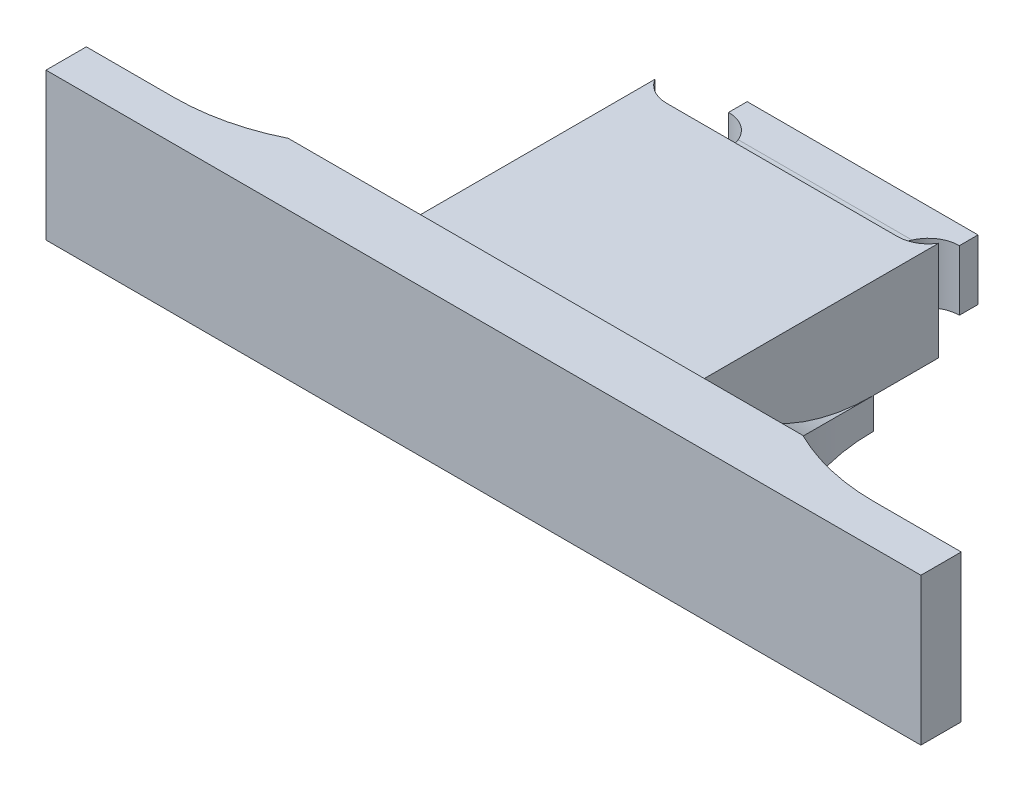
SolidWorks part; units mm, degrees
ref_plane "Front Plane" through (0, 0, 0) normal (0, 0, 1) x (1, 0, 0)
ref_plane "Top Plane" through (0, 0, 0) normal (0, 1, 0) x (1, 0, 0)
ref_plane "Right Plane" through (0, 0, 0) normal (1, 0, 0) x (0, 0, -1)
sketch "Sketch2" plane through (0, 0, 138.6086) normal (0, 0, 1) x (1, 0, 0)
  line L0 (70.4445, 0) -> (70.4445, 5) construction
  line L1 (-70.5526, 0) -> (70.4445, 0)
  line L2 (-70.5526, 0) -> (-70.5526, 23.7194)
  line L3 (-70.5526, 23.7194) -> (70.4445, 23.7194)
  line L4 (70.4445, 0) -> (70.4445, 23.7194)
extrude "Boss-Extrude1" add sketch "Sketch2" along normal blind 40
sketch "Sketch3" plane through (-70.5526, 0, 0) normal (-1, 0, 0) x (0, 0, 1)
  line L0 (138.6086, 23.7194) -> (138.6086, 0) construction
  line L3 (138.6086, 5) -> (152.3731, 5)
  line L4 (178.6086, 23.7194) -> (138.6086, 23.7194) construction
  line L5 (158.6086, 23.7194) -> (178.6086, 23.7194)
  line L8 (138.6086, 23.7194) -> (138.6086, 0)
  line L9 (138.6086, 0) -> (178.6086, 0)
  line L10 (178.6086, 0) -> (178.6086, 23.7194)
  line L11 (178.6086, 23.7194) -> (138.6086, 23.7194)
  line L12 (138.6086, 23.7194) -> (138.6086, 0)
  line L13 (138.6086, 0) -> (178.6086, 0)
  line L14 (178.6086, 0) -> (178.6086, 23.7194)
  line L15 (178.6086, 23.7194) -> (138.6086, 23.7194)
  arc A0 (138.6086, 5) -> (168.6086, 23.7194) centre (138.6086, 38.399) ccw
  point P2 (158.6086, 23.7194)
  point P21 (168.6086, 23.7194)
  line M6 (138.6086, 23.7194) -> (138.6086, 0)
  line M9 (178.6086, 23.7194) -> (138.6086, 23.7194)
  dimension "D2" = 5
  dimension "D3" = 23.7194
  dimension "D1" = 0
extrude "Cut-Extrude1" cut sketch "Sketch3" against normal through all contours M6 M9 region at (-70.5526, 16.0164, 150.4428)
sketch "Sketch4" plane through (0, 5, 0) normal (0, 1, 0) x (1, 0, 0)
  line L0 (-0.0541, -138.6086) -> (-0.0541, -183.6086)
  line L1 (70.4445, -138.6086) -> (-70.5526, -138.6086) construction
  line L2 (70.4445, -168.6086) -> (-70.5526, -168.6086) construction
  line L4 (-22.9249, -168.6086) -> (-22.9249, -128.1086)
  line L9 (-0.6345, -168.6086) -> (0.8576, -168.6086) construction
  line L10 (22.8168, -168.6086) -> (-22.9249, -168.6086)
  line L11 (22.8168, -168.6086) -> (22.8168, -128.1086)
  line L15 (-18.6541, -120.5086) -> (-18.6541, -117.5086)
  line L16 (-0.0541, -138.6086) -> (-0.0541, -118.0787) construction
  line L17 (-18.6541, -117.5086) -> (18.5459, -117.5086)
  line L19 (18.5459, -120.5086) -> (18.5459, -117.5086)
  circle A5 centre (18.5459, -125.5086) radius 5 construction
  arc A7 (18.5459, -120.5086) -> (22.8168, -128.1086) centre (18.5459, -125.5086) ccw
  circle A9 centre (-18.6541, -125.5086) radius 5
  arc A10 (-22.9249, -128.1086) -> (-18.6541, -120.5086) centre (-18.6541, -125.5086) ccw
  circle A11 centre (18.5459, -125.5086) radius 5
  arc A12 (18.5459, -120.5086) -> (22.8168, -128.1086) centre (18.5459, -125.5086) ccw
  point P31 (-0.0541, -117.5086)
  line M11 (-13.4387, -138.6086) -> (13.3306, -138.6086)
  arc M12 (13.3306, -138.6086) -> (8.0264, -116.1199) centre (18.5459, -125.5086) cw
  dimension "D3" = 3
  dimension "D1" = 0
  dimension "D4" = 0
extrude "Boss-Extrude2" add sketch "Sketch4" along normal blind 16 contours L17 M11 M12 | A7 L19 L17 L0 L10 L11 M12 M11 | A10 L4 L10 L0 L17 L15 M11 region at (11.7773, 5, 146.7916) region at (-9.2774, 5, 142.9696)
sketch "Sketch6" plane through (0, 23.7194, 0) normal (0, 1, 0) x (1, 0, 0)
  line L0 (-18.6541, -130.5086) -> (18.5459, -130.5086)
  line L1 (18.5459, -120.5086) -> (18.5459, -117.5086) construction
  line L2 (-18.6541, -117.5086) -> (18.5459, -117.5086) construction
  line L3 (-18.6541, -120.5086) -> (-18.6541, -117.5086) construction
  line L4 (18.5459, -117.5086) -> (18.5459, -120.5086)
  line L5 (-18.6541, -117.5086) -> (-18.6541, -120.5086)
  line L6 (18.5459, -117.5086) -> (-18.6541, -117.5086)
  arc A2 (18.5459, -120.5086) -> (22.8168, -128.1086) centre (18.5459, -125.5086) ccw construction
  arc A3 (-22.9249, -128.1086) -> (-18.6541, -120.5086) centre (-18.6541, -125.5086) ccw
  arc A4 (18.5459, -120.5086) -> (22.8168, -128.1086) centre (18.5459, -125.5086) ccw
  arc A5 (-22.9249, -128.1086) -> (-18.6541, -120.5086) centre (-18.6541, -125.5086) ccw construction
extrude "Cut-Extrude2" cut sketch "Sketch6" against normal blind 9 contours L0 region at (-0.0541, 23.7194, 123.7178)
fillet "Fillet1" radius 7 1 edges at (-0.0541, 14.7194, 130.5086)
sketch "Sketch10" plane through (0, 21, 0) normal (0, 1, 0) x (1, 0, 0)
  line L1 (-22.9249, -138.6086) -> (-22.9249, -167.1177) construction
  line L2 (-70.5526, -172.1086) -> (70.4445, -172.1086)
  line L3 (70.4445, -178.6086) -> (70.4445, -168.6086) construction
  line L4 (-70.5526, -168.6086) -> (-70.5526, -178.6086) construction
  line L5 (-0.0541, -167.1177) -> (-0.0541, -140.3068) construction
  line L6 (22.8168, -167.1177) -> (-22.9249, -167.1177) construction
  line L7 (70.4445, -168.6086) -> (70.4445, -178.6086)
  line L8 (70.4445, -178.6086) -> (-70.5526, -178.6086)
  line L9 (70.4445, -178.6086) -> (-70.5526, -178.6086) construction
  line L10 (-70.5526, -168.6086) -> (-70.5526, -178.6086)
  line L12 (-70.5526, -178.6086) -> (70.4445, -178.6086) construction
  line L13 (-22.9249, -138.6086) -> (-70.5526, -138.6086) construction
  line L16 (-70.5526, -138.6086) -> (-70.5526, -168.6086) construction
  line L17 (70.4445, -168.6086) -> (70.4445, -138.6086) construction
  line L18 (70.4445, -138.6086) -> (22.8168, -138.6086) construction
  line L19 (22.8168, -167.1177) -> (22.8168, -138.6086) construction
  line L20 (18.5459, -130.5086) -> (-18.6541, -130.5086) construction
  line L21 (-22.9249, -128.1086) -> (-22.9249, -167.1177) construction
  line L22 (22.8168, -167.1177) -> (22.8168, -128.1086) construction
  line L23 (70.4445, -178.6086) -> (70.4445, -168.6086)
  line L24 (-70.5526, -168.6086) -> (-70.5526, -178.6086)
  line L25 (-70.5526, -178.6086) -> (70.4445, -178.6086)
  line L26 (-22.9249, -138.6086) -> (-22.9249, -167.1177)
  line L27 (-22.9249, -138.6086) -> (-70.5526, -138.6086)
  line L28 (-70.5526, -138.6086) -> (-70.5526, -168.6086)
  line L29 (70.4445, -168.6086) -> (70.4445, -138.6086)
  line L30 (70.4445, -138.6086) -> (22.8168, -138.6086)
  line L31 (22.8168, -167.1177) -> (22.8168, -138.6086)
  line L32 (18.5459, -130.5086) -> (-18.6541, -130.5086)
  line L33 (-22.9249, -128.1086) -> (-22.9249, -167.1177)
  line L34 (22.8168, -167.1177) -> (22.8168, -128.1086)
  arc A0 (-22.9249, -138.6086) -> (-56.4249, -172.1086) centre (-56.4249, -138.6086) cw
  arc A2 (-22.9249, -128.1086) -> (-18.6541, -130.5086) centre (-18.6541, -125.5086) ccw construction
  arc A3 (18.5459, -130.5086) -> (22.8168, -128.1086) centre (18.5459, -125.5086) ccw construction
  arc A4 (-22.9249, -128.1086) -> (-18.6541, -130.5086) centre (-18.6541, -125.5086) ccw
  arc A5 (18.5459, -130.5086) -> (22.8168, -128.1086) centre (18.5459, -125.5086) ccw
  arc A6 (22.8168, -138.6086) -> (56.3168, -172.1086) centre (56.3168, -138.6086) ccw
  point P19 (-0.0541, -178.6086)
  dimension "D1" = 6.5
extrude "Cut-Extrude3" cut sketch "Sketch10" against normal through all both and the other way through all contours A0 L27 L28 L10 L2 | L30 A6 L2 L7 L29 region at (-49.6421, 21, 153.7111) region at (49.5339, 21, 153.7111)
